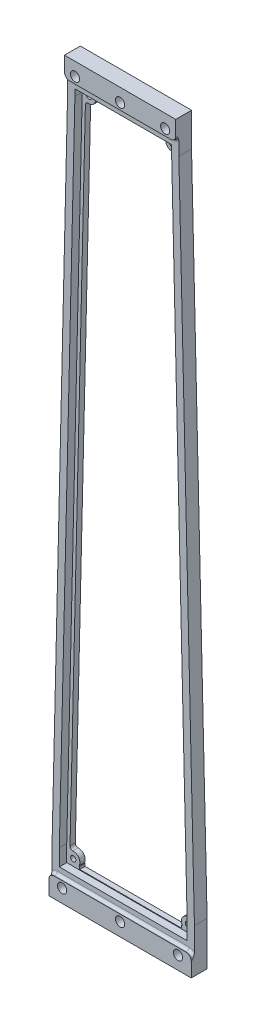
SolidWorks part; units mm, degrees
ref_plane "前视基准面" through (0, 0, 0) normal (0, 0, 1) x (1, 0, 0)
ref_plane "上视基准面" through (0, 0, 0) normal (0, 1, 0) x (1, 0, 0)
ref_plane "右视基准面" through (0, 0, 0) normal (1, 0, 0) x (0, 0, -1)
other "Configuration Table"
sketch "草图2" plane through (0, 0, -1.5384) normal (0, 0, -1) x (-1, 0, 0)
  line L2 (-17.1349, 121.1324) -> (-22.943, -124.6622)
  line L3 (-22.943, -124.6622) -> (-22.943, -124.7776)
  line L4 (-19.646, -129.6706) -> (-19.235, -129.6706)
  line L6 (22.943, -124.6622) -> (17.1349, 121.1324)
  line L8 (18.0521, 126.8606) -> (-18.0521, 126.8606)
  line L9 (-18.0521, 126.8606) -> (-18.0521, 124.6502)
  line L10 (-18.0521, 124.6502) -> (-23.943, -124.6504)
  line L11 (-23.943, -124.6504) -> (-23.943, -130.6706)
  line L12 (-23.943, -130.6706) -> (23.943, -130.6706)
  line L13 (23.943, -130.6706) -> (23.943, -124.6504)
  line L14 (23.943, -124.6504) -> (18.0521, 124.6499)
  line L15 (18.0521, 124.6499) -> (18.0521, 126.8606)
  line L16 (18.0521, 126.8606) -> (-18.0521, 126.8606)
  line L17 (-18.0521, 126.8606) -> (-18.0521, 124.6502)
  line L18 (-18.0521, 124.6502) -> (-23.943, -124.6504)
  line L19 (-23.943, -124.6504) -> (-23.943, -130.6706)
  line L20 (-23.943, -130.6706) -> (23.943, -130.6706)
  line L21 (23.943, -130.6706) -> (23.943, -124.6504)
  line L22 (23.943, -124.6504) -> (18.0521, 124.6499)
  line L23 (18.0521, 124.6499) -> (18.0521, 126.8606)
  line L24 (22.943, -124.9046) -> (22.943, -124.6622)
  line L25 (17.0521, 125.8606) -> (-17.0521, 125.8606) construction
  line L26 (-17.0521, 125.8606) -> (-17.0521, 124.6384) construction
  line L27 (-17.0521, 124.6384) -> (-22.943, -124.6622) construction
  line L28 (22.943, -124.6622) -> (17.0521, 124.6381) construction
  line L29 (17.0521, 124.6381) -> (17.0521, 125.8606) construction
  line L30 (12.2587, 125.8606) -> (-12.2587, 125.8606)
  line L31 (-22.943, -124.6622) -> (-22.943, -129.6706) construction
  line L32 (-22.943, -129.6706) -> (22.943, -129.6706) construction
  line L33 (22.943, -129.6706) -> (22.943, -124.6622) construction
  line L34 (-19.235, -130.6706) -> (-19.235, -129.6706)
  line L35 (-18.735, -130.4792) -> (-18.735, -126.2792) construction
  line L36 (19.265, -129.6706) -> (19.5656, -129.6706)
  line L37 (19.265, -129.6706) -> (19.265, -130.6706)
  line L38 (18.765, -125.8792) -> (18.765, -125.3792) construction
  circle A0 centre (21.717, -128.3973) radius 1 construction
  circle A1 centre (-21.717, -128.2703) radius 1 construction
  circle A2 centre (-15.748, 124.5872) radius 1 construction
  circle A3 centre (15.748, 124.5872) radius 1 construction
  circle A4 centre (21.717, -128.3973) radius 1 construction
  circle A5 centre (-21.717, -128.2703) radius 1 construction
  circle A6 centre (-15.748, 124.5872) radius 1 construction
  circle A7 centre (15.748, 124.5872) radius 1 construction
  circle A8 centre (-15.748, 124.5872) radius 1
  circle A9 centre (15.748, 124.5872) radius 1
  circle A10 centre (-21.717, -128.2703) radius 1
  circle A11 centre (21.717, -128.3973) radius 1
  arc A12 (-16.0246, 122.1026) -> (-13.2557, 124.7825) centre (-15.748, 124.5872) ccw
  arc A13 (-19.646, -129.6706) -> (-21.8784, -125.7755) centre (-21.717, -128.2703) ccw
  arc A14 (13.2557, 124.7825) -> (16.0246, 122.1026) centre (15.748, 124.5872) ccw
  arc A15 (21.8784, -125.9025) -> (19.5656, -129.6706) centre (21.717, -128.3973) ccw
  arc A16 (17.1349, 121.1324) -> (16.0246, 122.1026) centre (16.1352, 121.1087) ccw
  arc A17 (13.2557, 124.7825) -> (12.2587, 125.8606) centre (12.2587, 124.8606) ccw
  arc A18 (-13.2557, 124.7825) -> (-12.2587, 125.8606) centre (-12.2587, 124.8606) cw
  arc A19 (-17.1349, 121.1324) -> (-16.0246, 122.1026) centre (-16.1352, 121.1087) cw
  arc A20 (21.8784, -125.9025) -> (22.943, -124.9046) centre (21.943, -124.9046) ccw
  arc A21 (-21.8784, -125.7755) -> (-22.943, -124.7776) centre (-21.943, -124.7776) cw
  line M48 (18.0521, 126.8606) -> (-18.0521, 126.8606)
  line M49 (-18.0521, 126.8606) -> (-18.0521, 124.6502)
  line M50 (-18.0521, 124.6502) -> (-23.943, -124.6504)
  line M51 (-23.943, -124.6504) -> (-23.943, -130.6706)
  line M52 (-23.943, -130.6706) -> (23.943, -130.6706)
  line M53 (23.943, -130.6706) -> (23.943, -124.6504)
  line M54 (23.943, -124.6504) -> (18.0521, 124.6499)
  line M55 (18.0521, 124.6499) -> (18.0521, 126.8606)
  dimension "D3" = 2
  dimension "D4" = 2
  dimension "D5" = 2
  dimension "D6" = 2
  dimension "D7" = 2
  dimension "D8" = 5
  dimension "D9" = 5
  dimension "D10" = 5
  dimension "D12" = 5
  dimension "D13" = 1
  dimension "D11" = 1
  dimension "D15" = 0.5
  dimension "D16" = 0.5
  dimension "D17" = 1
  dimension "D1" = 0
  dimension "D2" = 1
extrude "凸台-拉伸1" add sketch "草图2" along normal blind 2 contours A13 A21 L3 L2 A19 A12 A18 L30 A17 A14 A16 L6 L24 A20 A15 L36 L37 L34 L4 A8 A9 A10 A11 M52 M53 M54 M55 M48 M49 M50 M51
sketch "草图3" plane through (0, 0, -3.5384) normal (0, 0, -1) x (-1, 0, 0)
  line L0 (26.943, -124.615) -> (21.0521, 124.6854)
  line L1 (21.0521, 124.6854) -> (21.0521, 129.8606)
  line L2 (21.0521, 129.8606) -> (-21.0521, 129.8606)
  line L3 (-21.0521, 129.8606) -> (-21.0521, 124.6857)
  line L4 (-21.0521, 124.6857) -> (-26.943, -124.615)
  line L5 (-26.943, -124.615) -> (-26.943, -133.6706)
  line L6 (-26.943, -133.6706) -> (26.943, -133.6706)
  line L7 (26.943, -133.6706) -> (26.943, -124.615)
  line L8 (18.0521, 126.8606) -> (-18.0521, 126.8606)
  line L9 (-18.0521, 126.8606) -> (-18.0521, 124.6502)
  line L10 (-18.0521, 124.6502) -> (-23.943, -124.6504)
  line L11 (-23.943, -124.6504) -> (-23.943, -130.6706)
  line L12 (-23.943, -130.6706) -> (23.943, -130.6706)
  line L13 (23.943, -130.6706) -> (23.943, -124.6504)
  line L14 (23.943, -124.6504) -> (18.0521, 124.6499)
  line L15 (18.0521, 124.6499) -> (18.0521, 126.8606)
  line L16 (18.0521, 126.8606) -> (-18.0521, 126.8606)
  line L17 (-18.0521, 126.8606) -> (-18.0521, 124.6502)
  line L18 (-18.0521, 124.6502) -> (-23.943, -124.6504)
  line L19 (-23.943, -124.6504) -> (-23.943, -130.6706)
  line L20 (-23.943, -130.6706) -> (23.943, -130.6706)
  line L21 (23.943, -130.6706) -> (23.943, -124.6504)
  line L22 (23.943, -124.6504) -> (18.0521, 124.6499)
  line L23 (18.0521, 124.6499) -> (18.0521, 126.8606)
  dimension "D1" = 0
  dimension "D2" = 3
extrude "凸台-拉伸2" add sketch "草图3" against normal blind 2
sketch "草图4" plane through (0, 0, -1.5384) normal (0, 0, 1) x (1, 0, 0)
  line L0 (-18.3021, 124.6529) -> (-24.193, -124.6474)
  line L1 (-24.193, -124.6474) -> (-24.193, -130.9206)
  line L2 (-24.193, -130.9206) -> (24.193, -130.9206)
  line L3 (24.193, -130.9206) -> (24.193, -124.6474)
  line L4 (24.193, -124.6474) -> (18.3021, 124.6532)
  line L5 (18.3021, 124.6532) -> (18.3021, 127.1106)
  line L6 (18.3021, 127.1106) -> (-18.3021, 127.1106)
  line L7 (-18.3021, 127.1106) -> (-18.3021, 124.6529)
  line L8 (-26.943, -124.615) -> (-26.943, -133.6706)
  line L9 (-26.943, -133.6706) -> (26.943, -133.6706)
  line L10 (26.943, -133.6706) -> (26.943, -124.615)
  line L11 (26.943, -124.615) -> (21.0521, 124.6857)
  line L12 (21.0521, 124.6857) -> (21.0521, 129.8606)
  line L13 (21.0521, 129.8606) -> (-21.0521, 129.8606)
  line L14 (-21.0521, 129.8606) -> (-21.0521, 124.6854)
  line L15 (-21.0521, 124.6854) -> (-26.943, -124.615)
  line L16 (-26.943, -124.615) -> (-26.943, -133.6706)
  line L17 (-26.943, -133.6706) -> (26.943, -133.6706)
  line L18 (26.943, -133.6706) -> (26.943, -124.615)
  line L19 (26.943, -124.615) -> (21.0521, 124.6857)
  line L20 (21.0521, 124.6857) -> (21.0521, 129.8606)
  line L21 (21.0521, 129.8606) -> (-21.0521, 129.8606)
  line L22 (-21.0521, 129.8606) -> (-21.0521, 124.6854)
  line L23 (-21.0521, 124.6854) -> (-26.943, -124.615)
  line L24 (-18.0521, 126.8606) -> (-18.0521, 124.6499)
  line L25 (-18.0521, 124.6499) -> (-23.943, -124.6504)
  line L26 (-23.943, -124.6504) -> (-23.943, -130.6706)
  line L27 (-23.943, -130.6706) -> (23.943, -130.6706)
  line L28 (23.943, -130.6706) -> (23.943, -124.6504)
  line L29 (23.943, -124.6504) -> (18.0521, 124.6502)
  line L30 (18.0521, 124.6502) -> (18.0521, 126.8606)
  line L31 (18.0521, 126.8606) -> (-18.0521, 126.8606)
  line L32 (-18.0521, 126.8606) -> (-18.0521, 124.6499)
  line L33 (-18.0521, 124.6499) -> (-23.943, -124.6504)
  line L34 (-23.943, -124.6504) -> (-23.943, -130.6706)
  line L35 (-23.943, -130.6706) -> (23.943, -130.6706)
  line L36 (23.943, -130.6706) -> (23.943, -124.6504)
  line L37 (23.943, -124.6504) -> (18.0521, 124.6502)
  line L38 (18.0521, 124.6502) -> (18.0521, 126.8606)
  line L39 (18.0521, 126.8606) -> (-18.0521, 126.8606)
  line M41 (-26.943, -124.615) -> (-26.943, -133.6706)
  line M42 (-26.943, -133.6706) -> (26.943, -133.6706)
  line M43 (26.943, -133.6706) -> (26.943, -124.615)
  line M44 (26.943, -124.615) -> (21.0521, 124.6857)
  line M45 (21.0521, 124.6857) -> (21.0521, 129.8606)
  line M46 (21.0521, 129.8606) -> (-21.0521, 129.8606)
  line M47 (-21.0521, 129.8606) -> (-21.0521, 124.6854)
  line M48 (-21.0521, 124.6854) -> (-26.943, -124.615)
  dimension "D1" = 0
  dimension "D2" = 0
  dimension "D3" = 0.25
extrude "凸台-拉伸3" add sketch "草图4" along normal blind 2.8 contours L7 L6 L5 L4 L3 L2 L1 L0 M48 M41 M42 M43 M44 M45 M46 M47
sketch "草图5" plane through (0, 0, 1.2616) normal (0, 0, 1) x (1, 0, 0)
  line L0 (-26.943, -133.6706) -> (26.943, -133.6706) construction
  line L1 (21.0521, 129.8606) -> (-21.0521, 129.8606) construction
  line L2 (-26.943, -133.6706) -> (26.943, -133.6706)
  line L3 (21.0521, 129.8606) -> (-21.0521, 129.8606)
  line L4 (-1021.0521, 132.3606) -> (48978.9479, 132.3606) construction
  line L5 (-21.0521, 129.8606) -> (21.0521, 129.8606)
  line L6 (-21.0521, 129.8606) -> (-21.0521, 134.8606)
  line L7 (-21.0521, 134.8606) -> (21.0521, 134.8606) construction
  line L8 (21.0521, 129.8606) -> (21.0521, 134.8606)
  line L9 (-26.943, -133.6706) -> (26.943, -133.6706)
  line L10 (-26.943, -133.6706) -> (-26.943, -138.6706)
  line L11 (-26.943, -138.6706) -> (26.943, -138.6706) construction
  line L12 (26.943, -133.6706) -> (26.943, -138.6706)
  line L13 (0, -865.1394) -> (0, 49134.8606) construction
  line L14 (-1026.943, -136.1706) -> (48973.057, -136.1706) construction
  line L16 (-21.0521, 134.8606) -> (21.0521, 134.8606) construction
  line L17 (-21.0521, 134.8606) -> (-21.0521, 137.3606)
  line L18 (-21.0521, 137.3606) -> (21.0521, 137.3606)
  line L19 (21.0521, 134.8606) -> (21.0521, 137.3606)
  line L20 (-26.943, -138.6706) -> (26.943, -138.6706) construction
  line L21 (-26.943, -138.6706) -> (-26.943, -141.1706)
  line L22 (-26.943, -141.1706) -> (26.943, -141.1706)
  line L23 (26.943, -138.6706) -> (26.943, -141.1706)
  circle A0 centre (-17.0521, 132.3606) radius 1.75
  circle A1 centre (17.0521, 132.3606) radius 1.75
  circle A2 centre (0, 132.3606) radius 1.75
  circle A3 centre (0, -136.1706) radius 1.75
  circle A4 centre (21.943, -136.1706) radius 1.75
  circle A5 centre (-21.943, -136.1706) radius 1.75
  point P11 (-21.0521, 132.3606)
  point P20 (0, 134.8606)
  point P25 (-26.943, -136.1706)
  line M17 (-26.943, -133.6706) -> (26.943, -133.6706)
  line M21 (21.0521, 129.8606) -> (-21.0521, 129.8606)
  dimension "D3" = 3.5
  dimension "D5" = 3.5
  dimension "D7" = 3.5
  dimension "D8" = 3.5
  dimension "D9" = 3.5
  dimension "D11" = 3.5
  dimension "D1" = 5
  dimension "D2" = 5
  dimension "D4" = 4
  dimension "D6" = 4
  dimension "D10" = 5
  dimension "D12" = 5
  dimension "D13" = 2.5
  dimension "D14" = 2.5
extrude "凸台-拉伸4" add sketch "草图5" against normal up to surface (4.8 mm away) contours L8 L7 L6 A2 A1 A0 M21 | L12 L10 L11 A5 A4 A3 M17
sketch "草图6" plane through (0, 0, 1.2616) normal (0, 0, 1) x (1, 0, 0)
  line L0 (-26.943, -138.6706) -> (-26.943, -141.1706) construction
  line L1 (-26.943, -133.6706) -> (-26.943, -138.6706) construction
  line L2 (-26.943, -141.1706) -> (26.943, -141.1706) construction
  line L3 (26.943, -138.6706) -> (26.943, -141.1706) construction
  line L4 (-26.943, -133.6706) -> (26.943, -133.6706) construction
  line L5 (26.943, -133.6706) -> (26.943, -138.6706) construction
  line L6 (21.0521, 129.8606) -> (21.0521, 134.8606) construction
  line L7 (21.0521, 134.8606) -> (21.0521, 137.3606) construction
  line L8 (-21.0521, 129.8606) -> (-21.0521, 134.8606) construction
  line L9 (-21.0521, 134.8606) -> (-21.0521, 137.3606) construction
  line L10 (21.0521, 129.8606) -> (-21.0521, 129.8606) construction
  line L11 (-21.0521, 137.3606) -> (21.0521, 137.3606) construction
  line L12 (-26.943, -138.6706) -> (-26.943, -141.1706)
  line L13 (-26.943, -135.6706) -> (-26.943, -138.6706)
  line L14 (-26.943, -141.1706) -> (26.943, -141.1706)
  line L15 (26.943, -138.6706) -> (26.943, -141.1706)
  line L16 (-24.943, -133.6706) -> (24.943, -133.6706)
  line L17 (26.943, -135.6706) -> (26.943, -138.6706)
  line L18 (21.0521, 131.8606) -> (21.0521, 134.8606)
  line L19 (21.0521, 134.8606) -> (21.0521, 137.3606)
  line L20 (-21.0521, 131.8606) -> (-21.0521, 134.8606)
  line L21 (-21.0521, 134.8606) -> (-21.0521, 137.3606)
  line L22 (19.0521, 129.8606) -> (-19.0521, 129.8606)
  line L23 (-21.0521, 137.3606) -> (21.0521, 137.3606)
  circle A0 centre (17.0521, 132.3606) radius 1.75 construction
  circle A1 centre (0, 132.3606) radius 1.75 construction
  circle A2 centre (-17.0521, 132.3606) radius 1.75 construction
  circle A3 centre (21.943, -136.1706) radius 1.75 construction
  circle A4 centre (0, -136.1706) radius 1.75 construction
  circle A5 centre (-21.943, -136.1706) radius 1.75 construction
  circle A6 centre (17.0521, 132.3606) radius 1.75
  circle A7 centre (0, 132.3606) radius 1.75
  circle A8 centre (-17.0521, 132.3606) radius 1.75
  circle A9 centre (21.943, -136.1706) radius 1.75
  circle A10 centre (0, -136.1706) radius 1.75
  circle A11 centre (-21.943, -136.1706) radius 1.75
  arc A12 (24.943, -133.6706) -> (26.943, -135.6706) centre (24.943, -135.6706) cw
  arc A13 (-26.943, -135.6706) -> (-24.943, -133.6706) centre (-24.943, -135.6706) cw
  arc A14 (21.0521, 131.8606) -> (19.0521, 129.8606) centre (19.0521, 131.8606) cw
  arc A15 (-21.0521, 131.8606) -> (-19.0521, 129.8606) centre (-19.0521, 131.8606) ccw
  dimension "D1" = 2
extrude "凸台-拉伸5" add sketch "草图6" along normal blind 1.2
fillet "圆角1" radius 1 6 edges at (26.3572, -134.2563, 1.2616) (-26.3572, -134.2563, 1.2616) (-20.4663, 130.4463, 1.2616) (20.4663, 130.4463, 1.2616) (0, -133.6706, 1.2616) (0, 129.8606, 1.2616)
